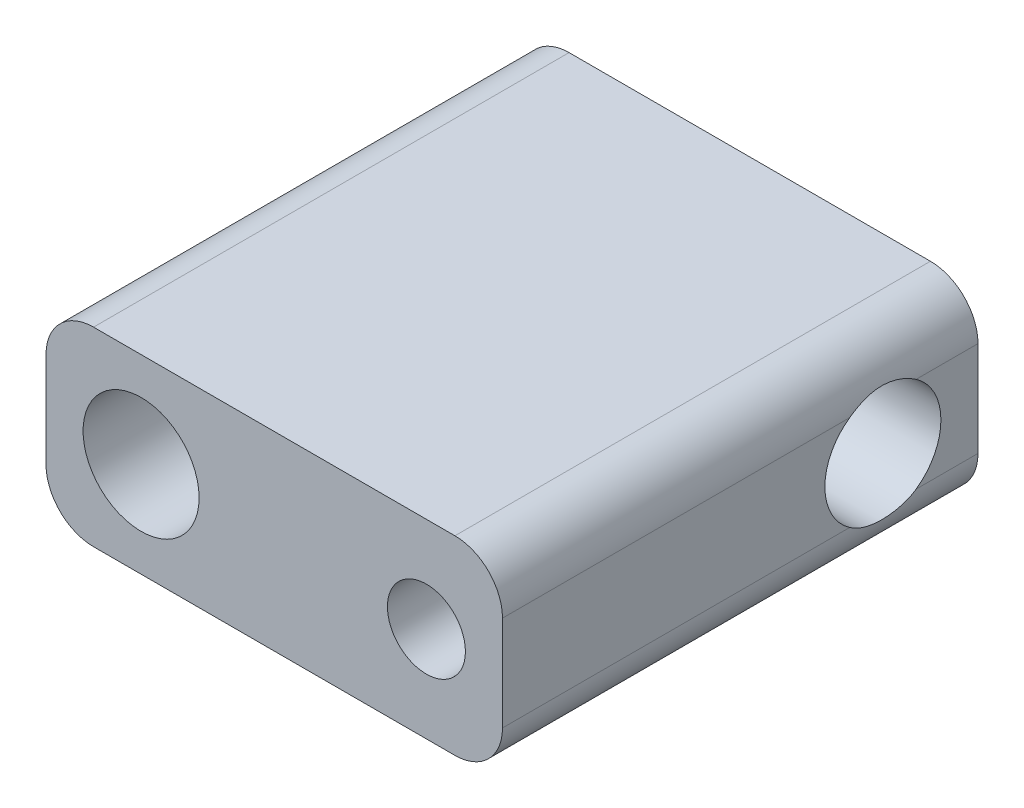
SolidWorks part; units mm, degrees
ref_plane "Front Plane" through (0, 0, 0) normal (0, 0, 1) x (1, 0, 0)
ref_plane "Top Plane" through (0, 0, 0) normal (0, 1, 0) x (1, 0, 0)
ref_plane "Right Plane" through (0, 0, 0) normal (1, 0, 0) x (0, 0, -1)
sketch "Sketch1" plane through (0, 0, 0) normal (0, 0, 1) x (1, 0, 0)
  line L1 (-24, 10) -> (24, 10)
  line L2 (-24, 10) -> (-24, -10)
  line L3 (-24, -10) -> (24, -10)
  line L4 (24, 10) -> (24, -10)
  line L5 (-24, 10) -> (24, -10) construction
  line L6 (-24, -10) -> (24, 10) construction
  circle A0 centre (-14, 0) radius 6.1
  circle A1 centre (16, 0) radius 4.1
  point P0 (0, 0)
  dimension "D3" = 12.2
  dimension "D4" = 10
  dimension "D5" = 8.2
  dimension "D6" = 8
  dimension "D1" = 20
  dimension "D2" = 48
extrude "Boss-Extrude1" add sketch "Sketch1" along normal blind 30
sketch "Sketch2" plane through (0, 0, 0) normal (0, 0, -1) x (-1, 0, 0)
  line L1 (-24, 10) -> (24, 10)
  line L2 (-24, 10) -> (-24, -10)
  line L3 (-24, -10) -> (24, -10)
  line L4 (24, 10) -> (24, -10)
extrude "Boss-Extrude2" add sketch "Sketch2" along normal blind 20
sketch "Sketch3" plane through (24, 0, 0) normal (1, 0, 0) x (0, 0, -1)
  line L0 (20, 10) -> (20, -10) construction
  circle A0 centre (10, 0) radius 6.1
  dimension "D1" = 12.2
  dimension "D2" = 10
extrude "Cut-Extrude1" cut sketch "Sketch3" against normal blind 40
fillet "Fillet1" radius 5 4 edges at (-24, -10, 5) (-24, 10, 5) (24, -10, 5) (24, 10, 5)
